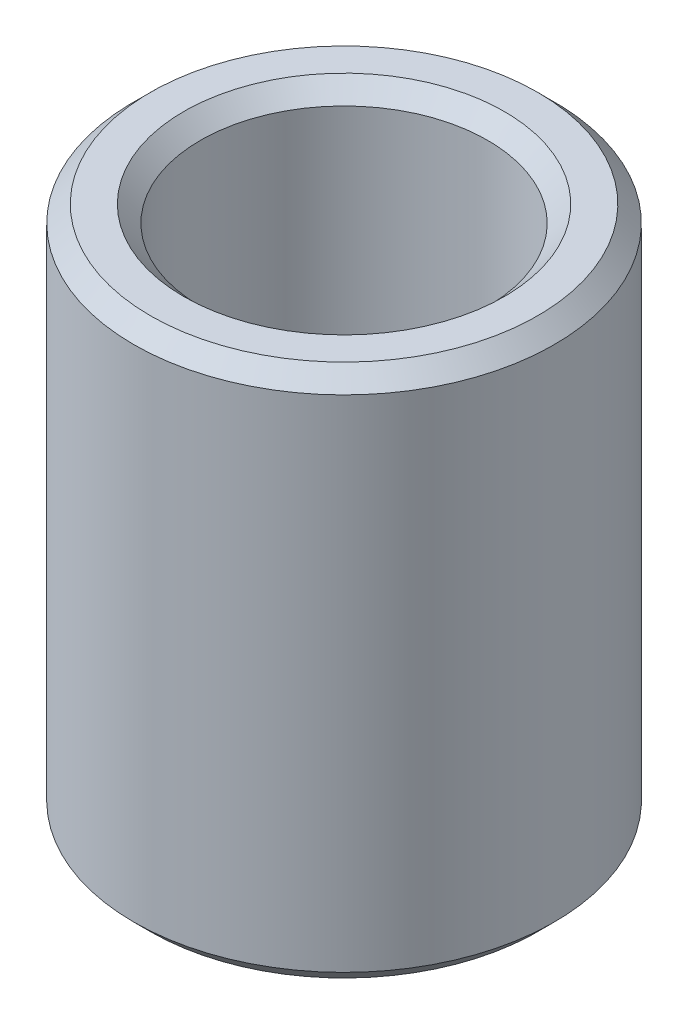
SolidWorks part; units mm, degrees
ref_plane "Front Plane" through (0, 0, 0) normal (0, 0, 1) x (1, 0, 0)
ref_plane "Top Plane" through (0, 0, 0) normal (0, 1, 0) x (1, 0, 0)
ref_plane "Right Plane" through (0, 0, 0) normal (1, 0, 0) x (0, 0, -1)
sketch "Sketch1" plane through (0, 0, 0) normal (0, 1, 0) x (1, 0, 0)
  circle A0 centre (0, 0) radius 35
  dimension "SLEEVE_OD" = 70
extrude "Boss-Extrude1" add sketch "Sketch1" along normal blind 88.7985
sketch "Sketch2" plane through (0, 0, 0) normal (0, 1, 0) x (1, 0, 0)
  circle A0 centre (0, 0) radius 23.9178
  dimension "BORE_D" = 47.8356
extrude "Cut-Extrude1" cut sketch "Sketch2" along normal through all
chamfer "Chamfer1" distance 2.7709 angle 45 4 edges at (0, 88.7985, 23.9178) (0, 0, 23.9178) (0, 0, 35) (0, 88.7985, 35)
